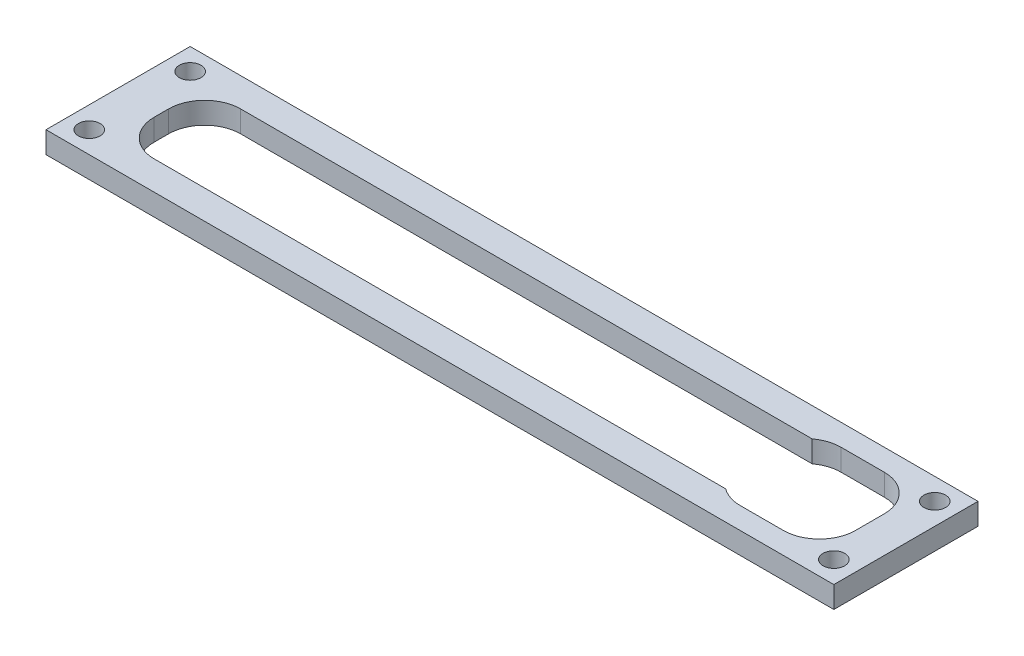
SolidWorks part; units mm, degrees
ref_plane "Front Plane" through (0, 0, 0) normal (0, 0, 1) x (1, 0, 0)
ref_plane "Top Plane" through (0, 0, 0) normal (0, 1, 0) x (1, 0, 0)
ref_plane "Right Plane" through (0, 0, 0) normal (1, 0, 0) x (0, 0, -1)
sketch "Sketch1" plane through (0, 0, 0) normal (0, 1, 0) x (1, 0, 0)
  line L0 (54.6479, 20) -> (54.6479, 0) construction
  line L1 (0, 0) -> (109.2958, 0)
  line L2 (0, 0) -> (0, 20)
  line L3 (0, 20) -> (109.2958, 20)
  line L4 (109.2958, 0) -> (109.2958, 20)
  line L5 (0, 10) -> (109.2958, 10) construction
  line L6 (54.6479, 16) -> (54.6479, 4) construction
  line L7 (6, 16) -> (103.2958, 16)
  line L8 (6, 16) -> (6, 4)
  line L9 (6, 4) -> (103.2958, 4)
  line L10 (103.2958, 16) -> (103.2958, 4)
  line L11 (6, 10) -> (103.2958, 10) construction
  circle A0 centre (3, 17) radius 1.5
  circle A1 centre (3, 3) radius 1.5
  circle A2 centre (106.2958, 3) radius 1.5
  circle A3 centre (106.2958, 17) radius 1.5
  point P17 (54.6479, 10)
  point P18 (54.6479, 10)
  dimension "D7" = 3
  dimension "D1" = 109.2958
  dimension "D2" = 20
  dimension "D3" = 97.2958
  dimension "D4" = 12
  dimension "D5" = 3
  dimension "D6" = 3
extrude "Boss-Extrude1" add sketch "Sketch1" along normal blind 3
sketch "Sketch2" plane through (0, 3, 0) normal (0, 1, 0) x (1, 0, 0)
  line L0 (92, 10) -> (-49908, 10) construction
  line L1 (103.2958, 4) -> (103.2958, 16) construction
  line L2 (90.2958, 17) -> (90.2958, 16)
  line L5 (103.2958, 16) -> (6, 16) construction
  line L6 (97.2958, 17) -> (97.2958, 3) construction
  line L7 (90.2958, 17) -> (104.2958, 17)
  line L9 (90.2958, 3) -> (104.2958, 3)
  line L10 (104.2958, 17) -> (104.2958, 3)
  line L12 (90.2958, 16) -> (103.2958, 16)
  line L13 (103.2958, 16) -> (103.2958, 4)
  line L14 (103.2958, 4) -> (90.2958, 4)
  line L15 (6, 4) -> (103.2958, 4) construction
  line L16 (90.2958, 4) -> (90.2958, 3)
  point P4 (103.2958, 10)
  point P23 (97.2958, 10)
  dimension "D1" = 1
  dimension "D2" = 14
  dimension "D3" = 14
extrude "Cut-Extrude1" cut sketch "Sketch2" against normal through all
fillet "Fillet1" radius 5 6 edges at (104.2958, 1.5, -17) (104.2958, 1.5, -3) (90.2958, 1.5, -17) (90.2958, 1.5, -3) (6, 1.5, -4) (6, 1.5, -16)
equation "\"TrackLength\"= ( ( \"n\" * 28 ) ) / cos ( \"MountAngle\" ) - ( 2 * \"x\" )"
equation "\"D1@Sketch1\"=\"TrackLength\""
equation "\"TrackWidth\"= \"MarbleTrackWidth\" + ( 2 * 4 )"
equation "\"D2@Sketch1\"=\"TrackWidth\""
equation "\"MarbleTrackWidth\"= \"MarbleWidth\" - 1"
equation "\"MarbleTrackLength\"= \"TrackLength\" - ( 2 * 6 )"
equation "\"D3@Sketch1\"=\"MarbleTrackLength\""
equation "\"D4@Sketch1\"=\"MarbleTrackWidth\""
equation "\"MarbleWidth\"= 13"
equation "\"n\"= 4"
equation "\"MountAngle\"= 10"
equation "\"x\"= 14 / cos ( \"MountAngle\" ) - 12"
